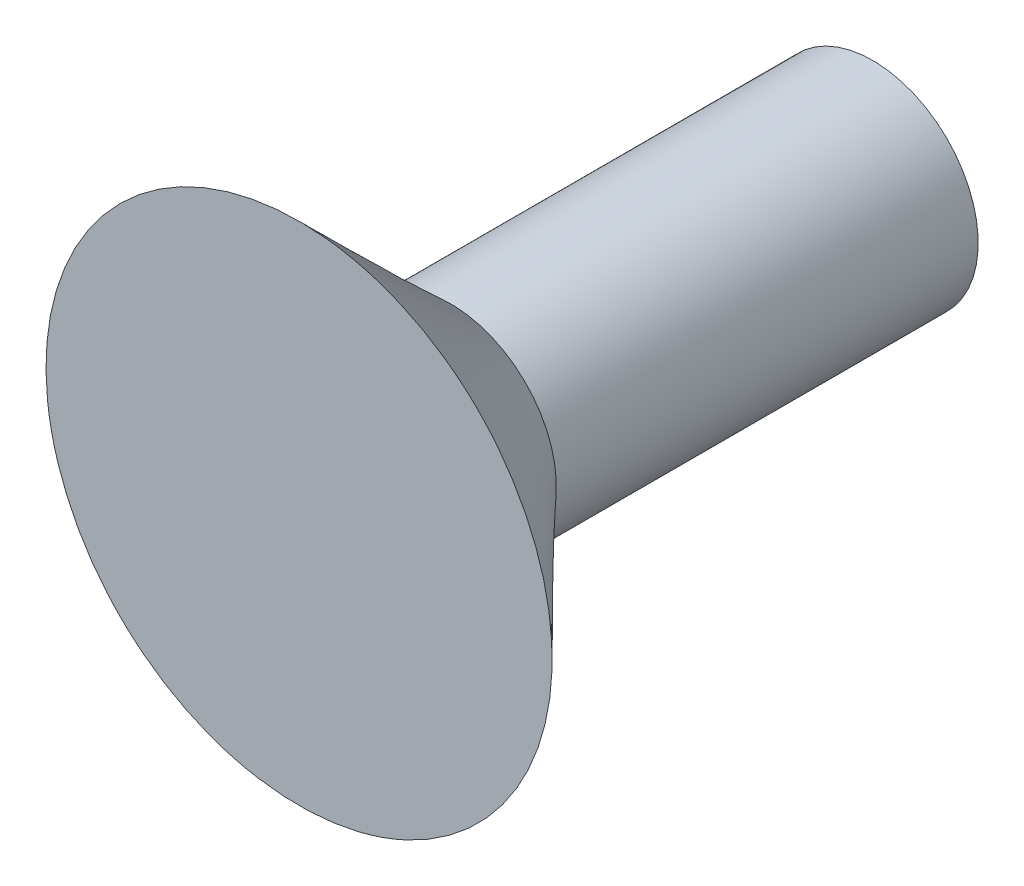
SolidWorks part; units mm, degrees
ref_plane "Płaszczyzna przednia" through (0, 0, 0) normal (0, 0, 1) x (1, 0, 0)
ref_plane "Płaszczyzna górna" through (0, 0, 0) normal (0, 1, 0) x (1, 0, 0)
ref_plane "Płaszczyzna prawa" through (0, 0, 0) normal (1, 0, 0) x (0, 0, -1)
sketch "Szkic3" plane through (0, 0, 0) normal (1, 0, 0) x (0, 0, -1)
  line L0 (-10.9908, 3.8045) -> (-9.1908, 3.8045)
  dimension "D1" = 1.8
ref_plane "Płaszczyzna1" through (0, 3.8045, 10.9908) normal (0, 0, -1) x (-1, 0, 0)
sketch "Szkic4" plane through (0, 3.8045, 10.9908) normal (0, 0, -1) x (-1, 0, 0)
  circle A0 centre (0, 0) radius 3
ref_plane "Płaszczyzna2" through (0, 3.8045, 9.1908) normal (0, 0, -1) x (-1, 0, 0)
sketch "Szkic5" plane through (0, 3.8045, 9.1908) normal (0, 0, -1) x (-1, 0, 0)
  circle A0 centre (0, 0) radius 1.25
loft "Wyciągnięcie po profilach1" add profiles "Szkic5", "Szkic4" connector at (0.8721, 4.7, 9.1908) connector at (1.47, 6.4197, 10.9908)
sketch "Szkic6" plane through (0, 0, 9.1908) normal (0, 0, -1) x (-1, 0, 0)
  circle A0 centre (0, 3.8045) radius 1.25
extrude "Dodanie-wyciągnięcie2" add sketch "Szkic6" along normal blind 5
